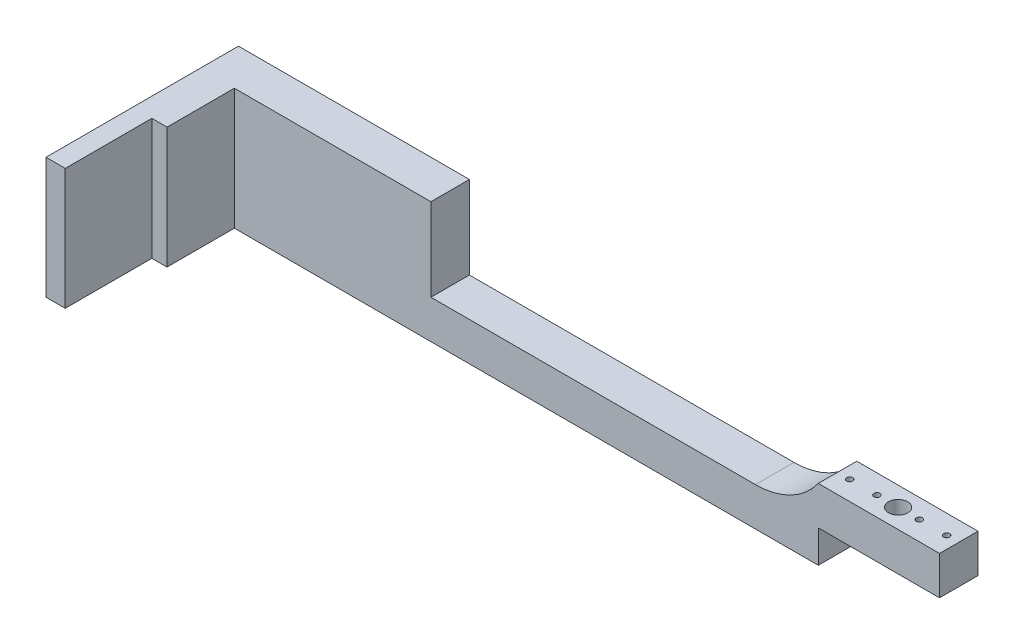
SolidWorks part; units mm, degrees
ref_plane "Front Plane" through (0, 0, 0) normal (0, 0, 1) x (1, 0, 0)
ref_plane "Top Plane" through (0, 0, 0) normal (0, 1, 0) x (1, 0, 0)
ref_plane "Right Plane" through (0, 0, 0) normal (1, 0, 0) x (0, 0, -1)
sketch "Sketch1" plane through (0, 0, 0) normal (0, 1, 0) x (1, 0, 0)
  circle A3 centre (0, -38.254) radius 38.254 construction
  circle A4 centre (0, -40.254) radius 40.254 construction
  circle A5 centre (0, -45.254) radius 45.254 construction
  dimension "D1" = 90.508
  dimension "D2" = 80.508
  dimension "D3" = 76.508
sketch "Sketch3" plane through (0, 0, 0) normal (0, 1, 0) x (1, 0, 0)
  line L0 (0, 0) -> (-40.254, 0)
  line L1 (-40.254, 0) -> (-40.254, -22.225)
  line L2 (-45.254, -22.225) -> (-45.254, -50.8)
  line L3 (-40.254, -22.225) -> (-45.254, -22.225)
  line L4 (-45.254, -50.8) -> (-51.604, -50.8)
  line L5 (-51.604, -50.8) -> (-51.604, 12.7)
  line L6 (-51.604, 12.7) -> (0, 12.7)
  line L7 (0, 12.7) -> (0, 0)
  circle A0 centre (0, -40.254) radius 40.254 construction
  circle A1 centre (0, -45.254) radius 45.254 construction
  dimension "D1" = 22.225
  dimension "D2" = 50.8
  dimension "D3" = 6.35
  dimension "D4" = 12.7
extrude "Boss-Extrude1" add sketch "Sketch3" along normal blind 12.7
sketch "Sketch5" plane through (0, 0, 0) normal (1, 0, 0) x (0, 0, -1)
  line L0 (12.7, 0) -> (12.7, 12.7) construction
  line L1 (0, 0) -> (12.7, 0)
  line L2 (0, 0) -> (0, 12.7)
  line L3 (0, 12.7) -> (12.7, 12.7)
  line L4 (12.7, 0) -> (12.7, 12.7)
extrude "Boss-Extrude2" add sketch "Sketch5" along normal blind 152.4
sketch "Sketch8" plane through (0, 12.7, 0) normal (0, 1, 0) x (1, 0, 0)
  line L0 (-40.254, 0) -> (152.4, 0) construction
  line L1 (152.4, 12.7) -> (192.4, 12.7)
  line L2 (152.4, 12.7) -> (152.4, 0)
  line L3 (152.4, 0) -> (192.4, 0)
  line L4 (152.4, 12.7) -> (152.4, 0) construction
  line L5 (192.4, 12.7) -> (192.4, 0)
  line L6 (172.4, 12.7) -> (172.4, 0) construction
  circle A0 centre (156.4, 6.35) radius 1
  circle A1 centre (165.4, 6.35) radius 1
  circle A4 centre (172.4, 6.35) radius 3.175
  circle A5 centre (188.4, 6.35) radius 1
  circle A6 centre (179.4, 6.35) radius 1
  point P9 (152.4, 6.35)
  dimension "D1" = 2
  dimension "D4" = 6.35
  dimension "D2" = 40
  dimension "D3" = 7
  dimension "D5" = 16
extrude "Boss-Extrude3" add sketch "Sketch8" against normal offset from surface (2 mm away) 10.7 up to face at (3.822, 0, 15.0813)
extrude "Boss-Extrude4" add sketch "Sketch8<2>" along normal offset from surface (10.7 mm away) 12.7 up to face at (172.4, 10.7, -6.35)
sketch "Sketch8<2>" plane through (0, 12.7, 0) normal (0, 1, 0) x (1, 0, 0) same geometry as "Sketch8"
fillet "Fillet1" radius 25.4 1 edges at (152.4, 12.7, -6.35)
sketch "Sketch9" plane through (0, 12.7, 0) normal (0, 1, 0) x (1, 0, 0)
  line L0 (24.596, 12.7) -> (24.596, 0)
  line L8 (-40.254, 0) -> (131.686, 0)
  line L9 (131.686, 0) -> (131.686, 12.7)
  line L10 (131.686, 12.7) -> (-51.604, 12.7)
  line L11 (-51.604, 12.7) -> (-51.604, -50.8)
  line L12 (-51.604, -50.8) -> (-45.254, -50.8)
  line L13 (-45.254, -50.8) -> (-45.254, -22.225)
  line L14 (-45.254, -22.225) -> (-40.254, -22.225)
  line L15 (-40.254, -22.225) -> (-40.254, 0)
  line L16 (-40.254, 0) -> (24.596, 0)
  line L18 (24.596, 12.7) -> (-51.604, 12.7)
  line L19 (-51.604, 12.7) -> (-51.604, -50.8)
  line L20 (-51.604, -50.8) -> (-45.254, -50.8)
  line L21 (-45.254, -50.8) -> (-45.254, -22.225)
  line L22 (-45.254, -22.225) -> (-40.254, -22.225)
  line L23 (-40.254, -22.225) -> (-40.254, 0)
  dimension "D2" = 76.2
  dimension "D1" = 0
extrude "Boss-Extrude5" add sketch "Sketch9" along normal blind 40 from surface starting at face at (3.822, 0, 15.0813)
equation "\"tightTol\"= 0.005in"
equation "\"normTol\"= 0.01in"
equation "\"looseTol\"= 0.02in"
equation "\"D1@Sketch1\"=\"looseTol\"+9cm"
equation "\"D2@Sketch1\"=8cm+\"looseTol\""
equation "\"D3@Sketch1\"=7.6cm+\"looseTol\""
equation "\"D2@Boss-Extrude1\"=0.875-10.7mm"
equation "\"D1@Sketch8\"= 2mm"
equation "\"D2@Sketch8\"=40mm"
equation "\"D3@Sketch8\"=7mm"
equation "\"D5@Sketch8\"=16mm"
equation "\"D1@Boss-Extrude3\"=10.7mm"
equation "\"D1@Boss-Extrude5\"=40mm"
